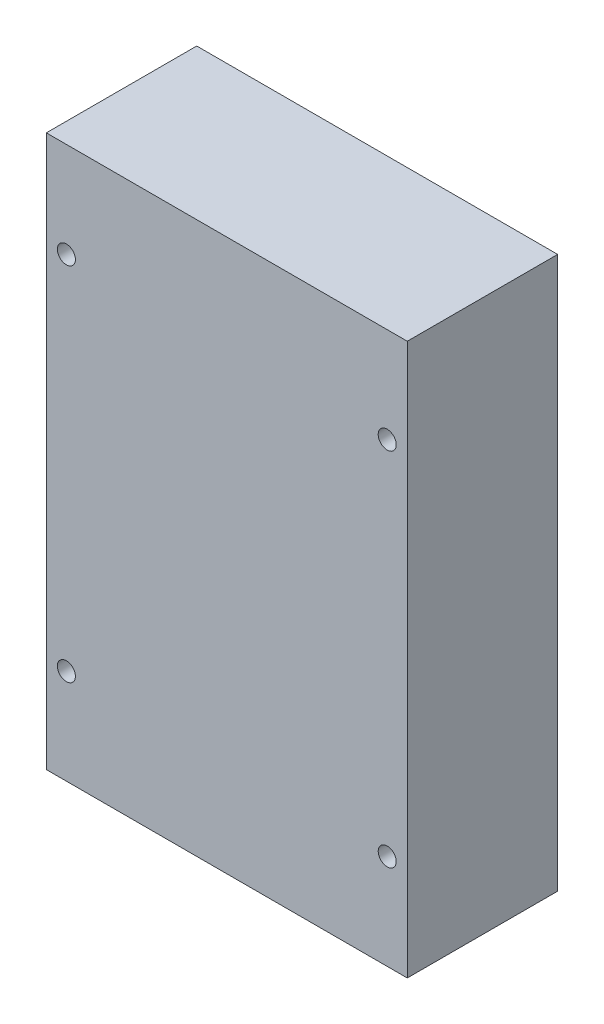
SolidWorks part; units mm, degrees
ref_plane "Plan de face" through (0, 0, 0) normal (0, 0, 1) x (1, 0, 0)
ref_plane "Plan de dessus" through (0, 0, 0) normal (0, 1, 0) x (1, 0, 0)
ref_plane "Plan de droite" through (0, 0, 0) normal (1, 0, 0) x (0, 0, -1)
sketch "Esquisse1" plane through (0, 0, 0) normal (0, 0, 1) x (1, 0, 0)
  line L1 (0, 0) -> (72, 0)
  line L2 (0, 0) -> (0, 110)
  line L3 (0, 110) -> (72, 110)
  line L4 (72, 0) -> (72, 110)
  dimension "D1" = 110
  dimension "D2" = 72
extrude "Boss.-Extru.1" add sketch "Esquisse1" along normal blind 30
sketch "Esquisse2" plane through (0, 0, 30) normal (0, 0, 1) x (1, 0, 0)
  line L0 (72, 110) -> (0, 110) construction
  line L4 (0, 110) -> (0, 0) construction
  circle A0 centre (4, 91) radius 1.5
  circle A1 centre (68, 91) radius 1.5
  circle A2 centre (4, 19) radius 1.5
  circle A3 centre (68, 19) radius 1.5
  point P10 (5.5706, 91)
  dimension "D1" = 3
  dimension "D2" = 3
  dimension "D3" = 3
  dimension "D4" = 3
  dimension "D5" = 64
  dimension "D6" = 72
  dimension "D7" = 19
  dimension "D8" = 4
hole_wizard "Dégagement M31" positions "Esquisse3" profile "Esquisse4" hole size "M3" standard "ISO" end condition through all
sketch "Esquisse3" plane through (0, 0, 30) normal (0, 0, 1) x (1, 0, 0)
  point P0 (4, 91)
  point P3 (68, 91)
  point P6 (4, 19)
  point P9 (68, 19)
sketch "Esquisse4" plane through (4, 91, 30) normal (1, 0, 0) x (0, -1, 0)
  line L0 (0, 0) -> (0, 30)
  line L1 (0, 30) -> (1.8, 30)
  line L2 (1.8, 30) -> (1.8, 0)
  line L5 (1.8, 0) -> (0, 0)
  line L11 (0, -6.35) -> (0, 107.95) construction
  dimension "Diamètre du perçage jusqu'au prochain" = 3.6
  dimension "Profondeur du perçage jusqu'au prochain" = 30
